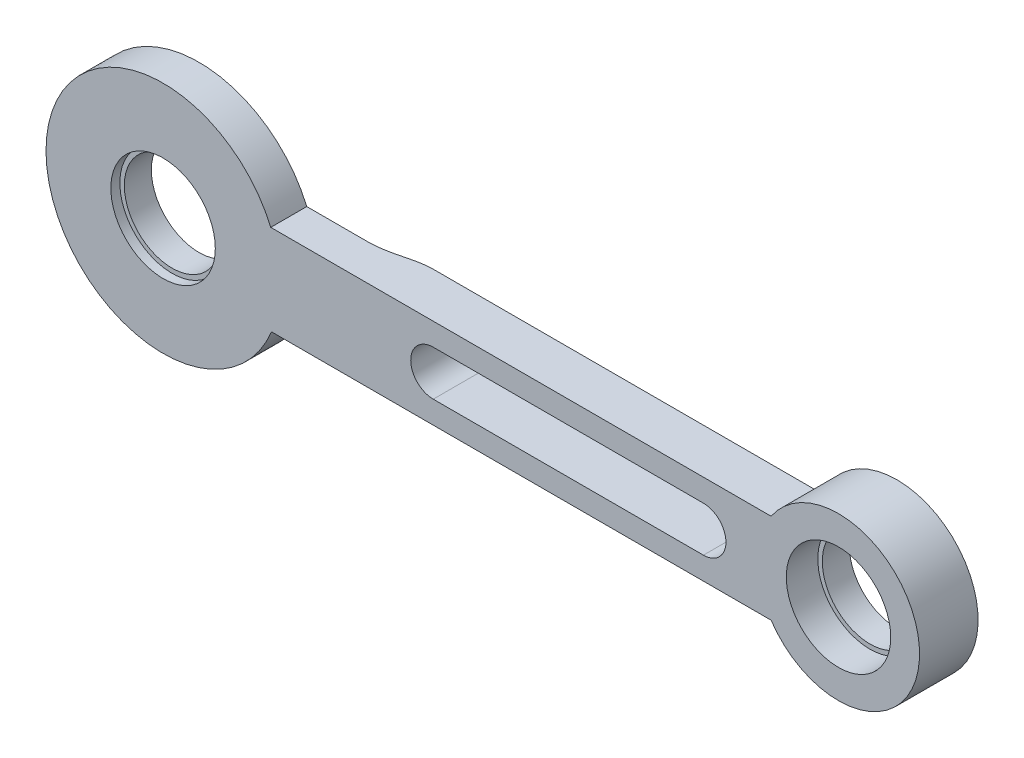
SolidWorks part; units mm, degrees
ref_plane "Front Plane" through (0, 0, 0) normal (0, 0, 1) x (1, 0, 0)
ref_plane "Top Plane" through (0, 0, 0) normal (0, 1, 0) x (1, 0, 0)
ref_plane "Right Plane" through (0, 0, 0) normal (1, 0, 0) x (0, 0, -1)
sketch "Sketch2" plane through (0, 0, 0) normal (0, 0, 1) x (1, 0, 0)
  line L0 (37.5, 0) -> (-37.5, 0) construction
  line L1 (30, 11.5622) -> (30, -14.1532) construction
  line L2 (37.5, -5) -> (-37.5, -5)
  line L3 (37.5, 5) -> (-37.5, 5)
  line L16 (7.5, 18.5485) -> (7.5, -21.0657) construction
  line L19 (-7.5, 0) -> (22.5, 0) construction
  line L21 (-7.5, 2.5) -> (22.5, 2.5)
  line L22 (-7.5, -2.5) -> (22.5, -2.5)
  arc A0 (37.5, -5) -> (37.5, 5) centre (37.5, 0) ccw
  arc A1 (-37.5, 5) -> (-37.5, -5) centre (-37.5, 0) ccw
  arc A2 (-7.5, 2.5) -> (-7.5, -2.5) centre (-7.5, 0) ccw
  arc A6 (22.5, -2.5) -> (22.5, 2.5) centre (22.5, 0) ccw
  point P5 (0, 0)
  point P16 (7.5, 0)
  dimension "D1" = 30
  dimension "D2" = 10
  dimension "D3" = 22.5
  dimension "D4" = 30
  dimension "D6" = 75
extrude "Boss-Extrude1" add sketch "Sketch2" along normal blind 5
sketch "Sketch11" plane through (0, 0, 5) normal (0, 0, 1) x (1, 0, 0)
  line L0 (22.5, -2.5) -> (22.5, -3) construction
  line L1 (-7.5, -2.5) -> (-7.5, -3) construction
  line L2 (22.5, -3) -> (-7.5, -3) construction
  text T0 "SIGNAL KNIGHTS" font "Century Gothic" height 1.5
sketch "Sketch12" plane through (0, 0, 0) normal (0, 0, -1) x (-1, 0, 0)
  circle A0 centre (-37.5, 0) radius 9
sketch "Sketch13" plane through (0, 0, 5) normal (0, 0, 1) x (1, 0, 0)
  circle A0 centre (-37.5, -0.1035) radius 9
extrude "Boss-Extrude2" add sketch "Sketch13" against normal blind 5
extrude "Boss-Extrude3" add sketch "Sketch12" against normal blind 5 and the other way blind 1.5 contours A0
sketch "Sketch16" plane through (0, 0, 5) normal (0, 0, 1) x (1, 0, 0)
  circle A0 centre (37.5, 0) radius 5.8
extrude "Cut-Extrude3" cut sketch "Sketch16" against normal blind 3.5
sketch "Sketch17" plane through (0, 0, 1.5) normal (0, 0, 1) x (1, 0, 0)
  circle A0 centre (37.5, 0) radius 5.3
extrude "Cut-Extrude4" cut sketch "Sketch17" against normal blind 7
sketch "Sketch18" plane through (0, 0, 0) normal (0, 0, -1) x (-1, 0, 0)
  circle A0 centre (37.5, -0.1035) radius 9
extrude "Cut-Extrude5" cut sketch "Sketch18" against normal blind 1
sketch "Sketch19" plane through (0, 0, 1) normal (0, 0, -1) x (-1, 0, 0)
  circle A0 centre (37.5, -0.1035) radius 5.3
extrude "Cut-Extrude6" cut sketch "Sketch19" against normal blind 3
sketch "Sketch20" plane through (0, 0, 5) normal (0, 0, 1) x (1, 0, 0)
  circle A0 centre (-37.5, -0.1035) radius 5.8
extrude "Cut-Extrude8" cut sketch "Sketch20" against normal blind 1
sketch "Sketch21" plane through (0, 0, 0) normal (0, 0, -1) x (-1, 0, 0)
  line L0 (17.5, 5) -> (17.5, -5)
  line L1 (17.5, 5) -> (30.0869, 5)
  line L2 (-30.0167, 5) -> (30.0869, 5) construction
  line L3 (17.5, -5) -> (29.9486, -5)
  line L4 (29.9486, -5) -> (-30.0167, -5) construction
  arc A1 (30.0869, 5) -> (29.9486, -5) centre (37.5, -0.1035) ccw
extrude "Cut-Extrude9" cut sketch "Sketch21" against normal blind 1
sketch "Sketch22" plane through (0, 0, 1) normal (0, 0, -1) x (-1, 0, 0)
  circle A0 centre (37.5, -0.1035) radius 13
  circle A1 centre (37.5, -0.1035) radius 9
extrude "Boss-Extrude4" add sketch "Sketch22" against normal blind 4
sketch "Sketch23" plane through (0, 0, 0) normal (0, 0, -1) x (-1, 0, 0)
  line L0 (17.5, 5) -> (17.5, -5) construction
  line L1 (12.5, 5) -> (17.5, 5)
  line L2 (17.5, 5) -> (17.5, 0)
  arc A0 (17.5, 0) -> (12.5, 5) centre (12.5, 0) ccw
  dimension "D1" = 5
extrude "Cut-Extrude10" cut sketch "Sketch23" against normal blind 1
sketch "Sketch24" plane through (0, 0, 0) normal (0, 0, -1) x (-1, 0, 0)
  line L1 (12.5, -5) -> (17.5, -5)
  line L2 (17.5, -5) -> (17.5, 0)
  arc A0 (12.5, -5) -> (17.5, 0) centre (12.5, 0) ccw
extrude "Cut-Extrude11" cut sketch "Sketch24" against normal blind 1
fillet "Fillet1" radius 5 1 edges at (-17.5, 0, 1)
